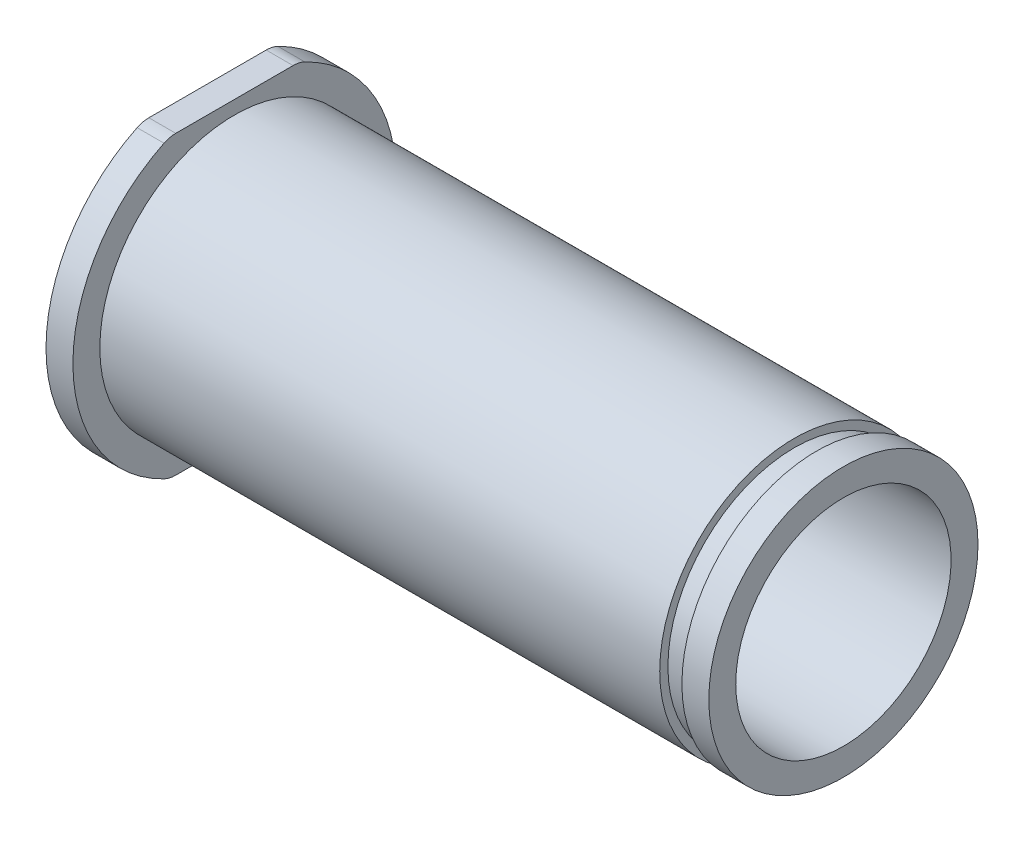
SolidWorks part; units mm, degrees
material "6061 Alloy"
ref_plane "Front Plane" through (0, 0, 0) normal (0, 0, 1) x (1, 0, 0)
ref_plane "Top Plane" through (0, 0, 0) normal (0, 1, 0) x (1, 0, 0)
ref_plane "Right Plane" through (0, 0, 0) normal (1, 0, 0) x (0, 0, -1)
sketch "Sketch1" plane through (0, 0, 0) normal (0, 0, 1) x (1, 0, 0)
  line L0 (0, 0) -> (75.0062, 0) construction
  line L1 (0, 19.05) -> (0, 12.7)
  line L2 (0, 12.7) -> (75.0062, 12.7)
  line L3 (75.0062, 12.7) -> (75.0062, 15.875)
  line L4 (75.0062, 15.875) -> (71.8312, 15.875)
  line L5 (71.8312, 15.875) -> (71.8312, 14.9098)
  line L6 (71.8312, 14.9098) -> (69.215, 14.9098)
  line L7 (69.215, 14.9098) -> (69.215, 15.875)
  line L8 (69.215, 15.875) -> (3.175, 15.875)
  line L9 (3.175, 15.875) -> (3.175, 19.05)
  line L10 (3.175, 19.05) -> (0, 19.05)
  dimension "D1" = 3.175
  dimension "D2" = 3.175
  dimension "D3" = 31.75
  dimension "D4" = 29.8196
  dimension "D5" = 2.6162
  dimension "D6" = 38.1
  dimension "D7" = 25.4
  dimension "D8" = 66.04
revolve "Revolve1" add sketch "Sketch1" angle 360 about L0
sketch "Sketch2" plane through (0, 0, 0) normal (-1, 0, 0) x (0, 0, 1)
  line L0 (0, 17.4625) -> (0, -17.4625) construction
  line L1 (-7.6134, 17.4625) -> (7.6134, 17.4625)
  line L2 (-7.6134, 17.4625) -> (-7.6134, 19.05)
  line L3 (-7.6134, 19.05) -> (7.6134, 19.05)
  line L4 (7.6134, 17.4625) -> (7.6134, 19.05)
  line L6 (-7.6134, -17.4625) -> (7.6134, -17.4625)
  line L7 (-7.6134, -17.4625) -> (-7.6134, -19.05)
  line L8 (-7.6134, -19.05) -> (7.6134, -19.05)
  line L9 (7.6134, -17.4625) -> (7.6134, -19.05)
  circle A0 centre (0, 0) radius 19.05 construction
  dimension "D1" = 38.1
  dimension "D2" = 34.925
extrude "Cut-Extrude1" cut sketch "Sketch2" against normal through all
fillet "Fillet1" radius 3.175 4 edges at (1.5875, -17.4625, -7.6134) (1.5875, -17.4625, 7.6134) (1.5875, 17.4625, 7.6134) (1.5875, 17.4625, -7.6134)
